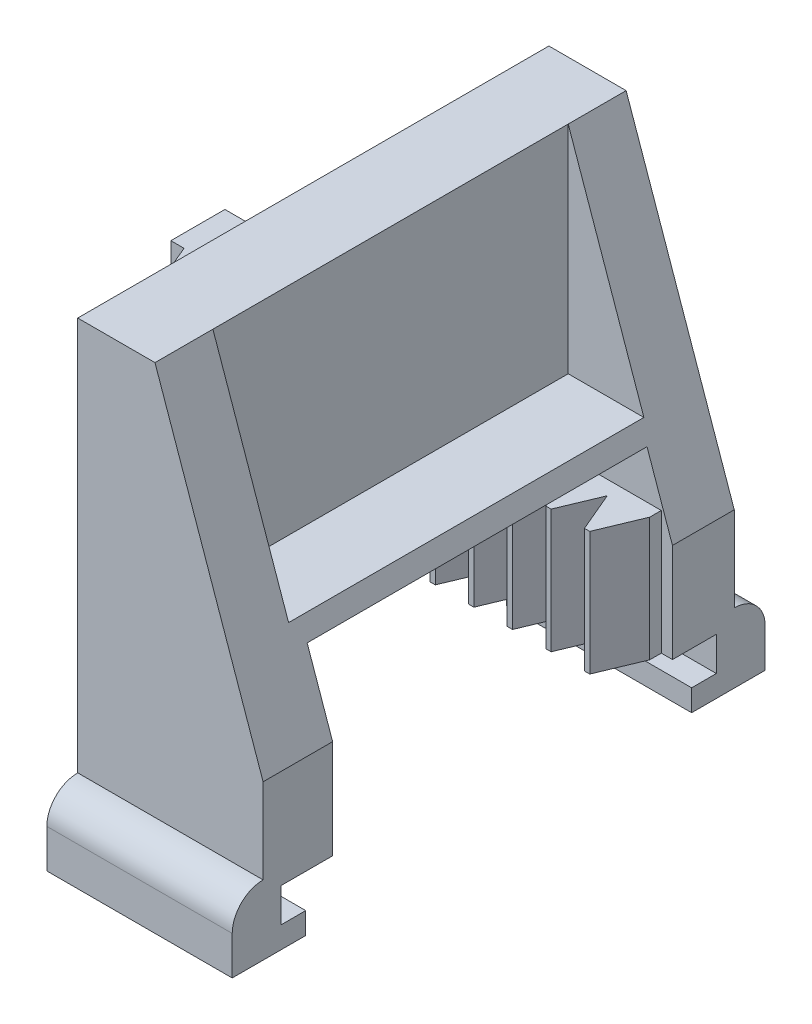
SolidWorks part; units mm, degrees
ref_plane "Front Plane" through (0, 0, 0) normal (0, 0, 1) x (1, 0, 0)
ref_plane "Top Plane" through (0, 0, 0) normal (0, 1, 0) x (1, 0, 0)
ref_plane "Right Plane" through (0, 0, 0) normal (1, 0, 0) x (0, 0, -1)
sketch "Sketch1" plane through (0, 0, 0) normal (0, 0, 1) x (1, 0, 0)
  line L0 (0, 0) -> (0, -30)
  line L1 (0, -30) -> (12, -30)
  line L2 (12, -30) -> (12, -20)
  line L3 (12, -20) -> (5, 0)
  line L4 (5, 0) -> (0, 0)
  dimension "D1" = 30
  dimension "D2" = 12
  dimension "D3" = 10
  dimension "D4" = 5
extrude "Boss-Extrude1" add sketch "Sketch1" against normal blind 30.5
sketch "Sketch4" plane through (0, 0, 0) normal (-1, 0, 0) x (0, 0, 1)
  line L0 (-30.5, 0) -> (-30.5, -30) construction
  line L1 (-26.5, -15.288) -> (-4.5, -15.288)
  line L2 (-26.5, -15.288) -> (-26.5, -30.288)
  line L3 (-26.5, -30.288) -> (-4.5, -30.288)
  line L4 (-4.5, -15.288) -> (-4.5, -30.288)
  point P4 (-26.5, -22.788)
  dimension "D1" = 22
  dimension "D2" = 15
  dimension "D3" = 4
extrude "Cut-Extrude2" cut sketch "Sketch4" against normal blind 25 contours L2 L1 L4 L3
ref_plane "Plane1" through (0, 0, -15.25) normal (0, 0, 1) x (1, 0, 0)
sketch "Sketch6" plane through (0, 0, -15.25) normal (0, 0, 1) x (1, 0, 0)
  line L0 (5, 0) -> (5, -14)
  line L1 (5, -14) -> (9.9, -14)
  line L2 (12, -20) -> (5, 0) construction
  line L3 (9.9, -14) -> (5, 0)
  dimension "D1" = 14
extrude "Cut-Extrude4" cut sketch "Sketch6" against normal mid plane 23
ref_plane "Plane2" through (0, -26.4, 0) normal (0, 1, 0) x (1, 0, 0)
sketch "Sketch7" plane through (0, -26.4, 0) normal (0, 1, 0) x (1, 0, 0)
  line L0 (11.2768, 29.25) -> (-19.7232, 29.25)
  line L62 (-16.5, 15.25) -> (16.5, 15.25) construction
  line L162 (11.2768, 29.25) -> (11.2768, 25.75)
  line L172 (-19.7232, 25.75) -> (-19.7232, 29.25)
  line L243 (11.2768, 25.75) -> (-19.7232, 25.75)
  dimension "D2" = 31
  dimension "D3" = 3.5
  dimension "D7" = 14
sketch "Sketch9" plane through (0, 0, 0) normal (-1, 0, 0) x (0, 0, 1)
  line L0 (-6.1597, -26.4) -> (-1.1597, -26.4)
  line L2 (-1.1597, -26.4) -> (-1.1597, -28.6)
  line L3 (-1.1597, -28.6) -> (-2.7597, -28.6)
  line L4 (-2.7597, -28.6) -> (-2.7597, -30.2967)
  line L5 (-2.7597, -30.2967) -> (-6.1597, -30.2967)
  line L6 (-6.1597, -30.2967) -> (-6.1597, -26.4)
  line L7 (-4.5, -30) -> (0, -30) construction
  line L15 (-15.25, -6.6) -> (-15.25, 6.6) construction
  line L16 (-27.7403, -30.2967) -> (-24.3403, -30.2967)
  line L17 (-27.7403, -28.6) -> (-27.7403, -30.2967)
  line L18 (-29.3403, -28.6) -> (-27.7403, -28.6)
  line L19 (-29.3403, -26.4) -> (-29.3403, -28.6)
  line L20 (-24.3403, -26.4) -> (-29.3403, -26.4)
  line L21 (-24.3403, -30.2967) -> (-24.3403, -26.4)
  point P2 (-7.8007, -26.4)
  point P3 (-6.1597, -26.4)
  point P18 (0, 0)
  point P19 (-4.5, -26.4)
  dimension "D1" = 5
  dimension "D2" = 2.2
  dimension "D3" = 1.4
  dimension "D4" = 1.6
extrude "Boss-Extrude3" add sketch "Sketch7" along normal blind 8
sketch "Sketch10" plane through (0, -18.4, 0) normal (0, 1, 0) x (1, 0, 0)
  line L0 (11.2768, 25.75) -> (10.1347, 23.0104)
  line L2 (10.1347, 23.0104) -> (9.7913, 23.0104)
  line L3 (9.7913, 23.0104) -> (8.6309, 25.75)
  line L4 (-19.7232, 25.75) -> (11.2768, 25.75) construction
  line L5 (8.6309, 25.75) -> (11.2768, 25.75)
  point P3 (10.1295, 22.9979)
  point P4 (9.7913, 23.0104)
extrude "Boss-Extrude4" add sketch "Sketch10" against normal up to vertex (8 mm away) up to point (11.2768, -26.4, -25.75)
pattern_linear "LPattern1" count 12 spacing 2.5 along (-1, 0, 0) of "Boss-Extrude4"
sketch "Sketch11" plane through (0, 0, -30.5) normal (0, 0, -1) x (-1, 0, 0)
  line L0 (-12, -30) -> (-12, -20) construction
  line L1 (-12, -25.5) -> (0, -25.5)
  line L2 (-12, -25.5) -> (-12, -30)
  line L3 (-12, -30) -> (0, -30)
  line L4 (0, -25.5) -> (0, -30)
  dimension "D1" = 4.5
extrude "Boss-Extrude5" add sketch "Sketch11" along normal blind 2
fillet "Fillet1" radius 2 1 edges at (6, -25.5, -32.5)
mirror "Mirror1" about plane through (0, 0, -15.25) normal (0, 0, 1) of "Boss-Extrude5"
fillet "Fillet2" radius 2 1 edges at (6, -25.5, 2)
extrude "Cut-Extrude5" cut sketch "Sketch9" against normal through all
